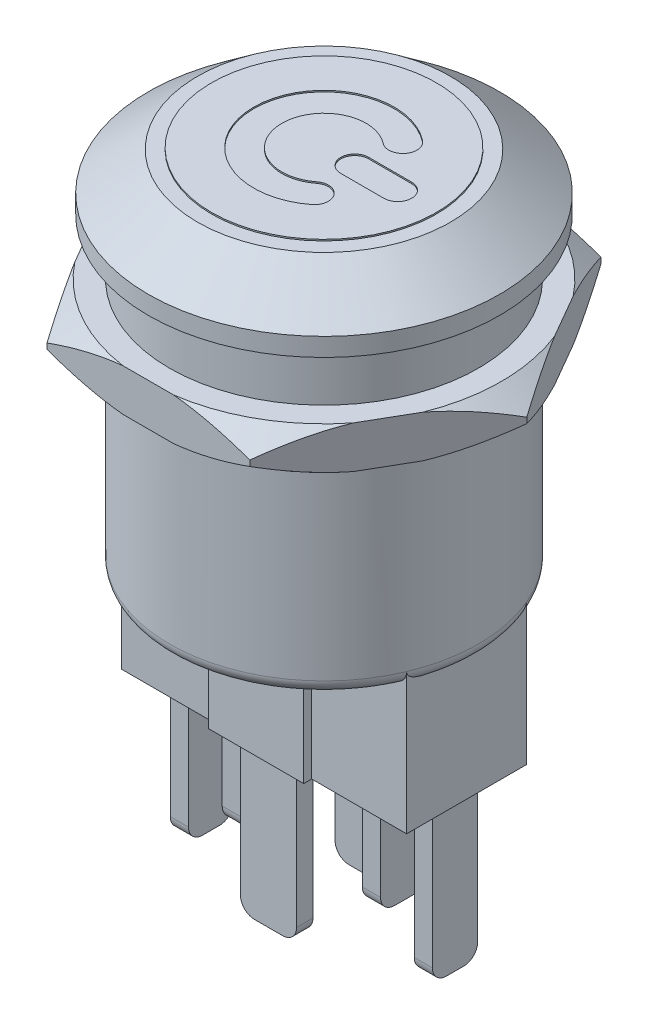
SolidWorks part; units mm, degrees
note: '?' marks a value the reader was unsure of.
ref_plane "前视基准面" through (0, 0, 0) normal (0, 0, 1) x (1, 0, 0)
ref_plane "上视基准面" through (0, 0, 0) normal (0, 1, 0) x (1, 0, 0)
ref_plane "右视基准面" through (0, 0, 0) normal (1, 0, 0) x (0, 0, -1)
sketch "草图1" plane through (0, 0, 0) normal (0, 1, 0) x (1, 0, 0)
  circle A0 centre (0, 0) radius 11
  dimension "D1" = 22
extrude "凸台-拉伸1" add sketch "草图1" along normal blind 15
sketch "草图8" plane through (0, 0, 0) normal (0, -1, 0) x (1, 0, 0)
  line L0 (-3.3825, 4.2596) -> (-3.3825, 4.8256)
  line L1 (10.1418, -4.2596) -> (3.3825, -4.2596)
  line L2 (10.1418, -4.2596) -> (10.1418, 4.2596)
  line L3 (10.1418, 4.2596) -> (3.3825, 4.2596)
  line L4 (-10.1418, -4.2596) -> (-10.1418, 4.2596)
  line L5 (10.1418, -4.2596) -> (-10.1418, 4.2596) construction
  line L6 (10.1418, 4.2596) -> (-10.1418, -4.2596) construction
  line L7 (-3.3825, -4.8256) -> (3.3825, -4.8256)
  line L8 (-3.3825, -4.8256) -> (-3.3825, -4.2596)
  line L9 (-3.3825, 4.8256) -> (3.3825, 4.8256)
  line L10 (3.3825, -4.8256) -> (3.3825, -4.2596)
  line L11 (-3.3825, -4.8256) -> (3.3825, 4.8256) construction
  line L12 (-3.3825, 4.8256) -> (3.3825, -4.8256) construction
  line L13 (-3.3825, -4.2596) -> (-10.1418, -4.2596)
  line L14 (-3.3825, 4.2596) -> (-10.1418, 4.2596)
  line L15 (3.3825, 4.2596) -> (3.3825, 4.8256)
  circle A0 centre (0, 0) radius 11 construction
  point P0 (0, 0)
  point P8 (0, 0)
extrude "凸台-拉伸5" add sketch "草图8" along normal blind 9
sketch "草图2" plane through (0, 0, 0) normal (0, -1, 0) x (1, 0, 0)
  line L0 (0, 0) -> (0, 7.9124) construction
  line L1 (3.6947, 0) -> (-4.9885, 0) construction
  line L2 (-5.6352, 1.6103) -> (-4.3417, 1.6103)
  line L3 (-4.3417, -1.6103) -> (-4.3417, 1.6103)
  line L4 (-5.6352, -1.6103) -> (-5.6352, 1.6103)
  line L5 (-5.6352, -1.6103) -> (-4.3417, -1.6103)
  line L6 (5.6352, -1.6103) -> (4.3417, -1.6103)
  line L7 (0, 0) -> (-8.6832, 0) construction
  line L8 (9.33, 1.6103) -> (8.0364, -1.6103) construction
  line L9 (9.33, -1.6103) -> (8.0364, 1.6103) construction
  line L10 (5.6352, 1.6103) -> (4.3417, 1.6103)
  line L11 (4.3417, -1.6103) -> (4.3417, 1.6103)
  line L12 (8.0364, -1.6103) -> (8.0364, 1.6103)
  line L13 (-9.33, -1.6103) -> (-8.0364, -1.6103)
  line L14 (-9.33, -1.6103) -> (-9.33, 1.6103)
  line L15 (-9.33, 1.6103) -> (-8.0364, 1.6103)
  line L16 (-8.0364, -1.6103) -> (-8.0364, 1.6103)
  line L17 (-9.33, -1.6103) -> (-8.0364, 1.6103) construction
  line L18 (-9.33, 1.6103) -> (-8.0364, -1.6103) construction
  line L19 (9.33, 1.6103) -> (8.0364, 1.6103)
  line L20 (9.33, -1.6103) -> (9.33, 1.6103)
  line L21 (9.33, -1.6103) -> (8.0364, -1.6103)
  line L22 (5.6352, -1.6103) -> (5.6352, 1.6103)
  line L23 (1.9974, -2.7841) -> (1.9974, -3.9524)
  line L24 (1.9974, 2.7841) -> (-1.9974, 2.7841)
  line L25 (1.9974, 2.7841) -> (1.9974, 3.9524)
  line L26 (1.9974, 3.9524) -> (-1.9974, 3.9524)
  line L27 (-1.9974, 2.7841) -> (-1.9974, 3.9524)
  line L28 (1.9974, 2.7841) -> (-1.9974, 3.9524) construction
  line L29 (1.9974, 3.9524) -> (-1.9974, 2.7841) construction
  line L30 (1.9974, -2.7841) -> (-1.9974, -2.7841)
  line L31 (1.9974, -3.9524) -> (-1.9974, -3.9524)
  line L32 (-1.9974, -2.7841) -> (-1.9974, -3.9524)
  point P0 (0, 3.3682)
  point P10 (-8.6832, 0)
  point P23 (8.6832, 0)
  dimension "D1" = 2
extrude "凸台-拉伸2" add sketch "草图2" along normal blind 11 from surface at 9 starting at face at (0, -9, 0)
sketch "草图9" plane through (0, 15, 0) normal (0, 1, 0) x (1, 0, 0)
  line L1 (-7.2169, 12.5) -> (-14.4338, 0)
  line L2 (-14.4338, 0) -> (-7.2169, -12.5)
  line L3 (-7.2169, -12.5) -> (7.2169, -12.5)
  line L4 (7.2169, -12.5) -> (14.4338, 0)
  line L5 (14.4338, 0) -> (7.2169, 12.5)
  line L6 (7.2169, 12.5) -> (-7.2169, 12.5)
  circle A0 centre (0, 0) radius 12.5 construction
  circle A1 centre (0, 0) radius 12.5 construction
  dimension "D1" = 25
extrude "凸台-拉伸6" add sketch "草图9" along normal blind 3
sketch "草图10" plane through (0, 18, 0) normal (0, 1, 0) x (1, 0, 0)
  circle A0 centre (0, 0) radius 12.5
  dimension "D1" = 25
extrude "凸台-拉伸7" add sketch "草图10" along normal blind 8
chamfer "倒角2" distance 2.7 distance2 3.5 1 edges at (0, 26, 12.5) first distance on face at (0, 26, 12.5)
sketch "草图12" plane through (0, 0, 0) normal (0, 0, 1) x (1, 0, 0)
  line L0 (-12.6295, 18) -> (-14.4338, 16.7)
  line L1 (-14.4338, 18) -> (-10.8253, 18) construction
  line L2 (-14.4338, 18) -> (-14.4338, 15) construction
  line L3 (-14.4338, 16.5) -> (-11.8121, 16.5) construction
  line L4 (-12.6295, 15) -> (-14.4338, 16.3)
  line L5 (-12.6295, 18) -> (-12.6295, 18.5)
  line L6 (-12.6295, 18.5) -> (-14.9338, 18.5)
  line L7 (-14.9338, 18.5) -> (-14.9338, 14.5)
  line L8 (-14.9338, 14.5) -> (-12.6295, 14.5)
  line L9 (-12.6295, 14.5) -> (-12.6295, 15)
  line L10 (-14.4338, 16.7) -> (-14.4338, 16.3)
  line L11 (0, 15) -> (0, 29.2248) construction
  line L12 (-11, 15) -> (11, 15) construction
  dimension "D1" = 1.3
  dimension "D2" = 0.5
  dimension "D3" = 0.5
  dimension "D4" = 0.5
revolve "切除-旋转1" cut sketch "草图12" angle 360 about L11
fillet "圆角2" radius 1 2 edges at (0, 0, -11) (0, 0, 11)
fillet "圆角3" radius 1 2 edges at (11, 0, 0) (-11, 0, 0)
sketch "草图13" plane through (0, 26, 0) normal (0, 1, 0) x (1, 0, 0)
  circle A0 centre (0, 0) radius 8
  dimension "D1" = 16
extrude "凸台-拉伸8" add sketch "草图13" along normal blind 0.1
sketch "草图14" plane through (0, 26.1, 0) normal (0, 1, 0) x (1, 0, 0)
  line L0 (5.2502, 0) -> (2.1899, 0) construction
  line L1 (5.2502, -0.9936) -> (2.1899, -0.9936)
  line L2 (5.2502, 0.9936) -> (2.1899, 0.9936)
  line L3 (2.3801, 1.8263) -> (3.9668, 3.0438)
  line L4 (2.3801, -1.8263) -> (3.9668, -3.0438)
  arc A0 (2.3801, 1.8263) -> (2.3801, -1.8263) centre (0, 0) ccw
  arc A1 (3.9668, 3.0438) -> (3.9668, -3.0438) centre (0, 0) ccw
  arc A2 (5.2502, -0.9936) -> (5.2502, 0.9936) centre (5.2502, 0) ccw
  arc A3 (2.1899, 0.9936) -> (2.1899, -0.9936) centre (2.1899, 0) ccw
  circle A4 centre (0, 0) radius 5 construction
  circle A5 centre (0, 0) radius 3 construction
  point P7 (3.72, 0)
  dimension "D1" = 6
  dimension "D3" = 75
  dimension "D2" = 2
extrude "切除-拉伸3" cut sketch "草图14" against normal blind 0.1
fillet "圆角4" radius 1 4 edges at (2.3801, 26.05, 1.8263) (3.9668, 26.05, 3.0438) (2.3801, 26.05, -1.8263) (3.9668, 26.05, -3.0438)
fillet "圆角5" radius 1 12 edges at (-8.6832, -20, -1.6103) (-8.6832, -20, 1.6103) (-4.9885, -20, -1.6103) (-4.9885, -20, 1.6103) (1.9974, -20, 3.3682) (-1.9974, -20, 3.3682) (-1.9974, -20, -3.3682) (1.9974, -20, -3.3682) (4.9885, -20, -1.6103) (4.9885, -20, 1.6103) (8.6832, -20, -1.6103) (8.6832, -20, 1.6103)
sketch "草图15" plane through (0, 18, 0) normal (0, 1, 0) x (1, 0, 0)
  circle A1 centre (0, 0) radius 12.5
  circle A2 centre (0, 0) radius 11
  circle A3 centre (0, 0) radius 11 construction
  circle A4 centre (0, 0) radius 12.5 construction
extrude "切除-拉伸4" cut sketch "草图15" along normal blind 4
sketch "草图16" plane through (0, 0, -3.9524) normal (0, 0, -1) x (-1, 0, 0)
  text T0 " LED"
extrude "切除-拉伸5" cut sketch "草图16" against normal blind 0.1
sketch "草图17" plane through (0, 0, -1.6103) normal (0, 0, -1) x (-1, 0, 0)
  line L0 (-4.3417, -19) -> (-4.3417, -9) construction
  line L1 (-5.6352, -20) -> (-4.3417, -20)
  line L2 (-5.6352, -20) -> (-5.6352, -17.5)
  line L3 (-5.6352, -17.5) -> (-4.3417, -17.5)
  line L4 (-4.3417, -20) -> (-4.3417, -17.5)
  line L5 (5.6352, -19) -> (5.6352, -9) construction
  line L6 (4.3417, -20) -> (5.6352, -20)
  line L7 (4.3417, -20) -> (4.3417, -17.5)
  line L8 (4.3417, -17.5) -> (5.6352, -17.5)
  line L9 (5.6352, -20) -> (5.6352, -17.5)
  dimension "D1" = 2.5
extrude "切除-拉伸6" cut sketch "草图17" against normal through all
fillet "圆角6" radius 1 4 edges at (-4.9885, -17.5, 1.6103) (-4.9885, -17.5, -1.6103) (4.9885, -17.5, -1.6103) (4.9885, -17.5, 1.6103)
sketch "草图18" plane through (0, -20, 0) normal (0, -1, 0) x (1, 0, 0)
  point P0 (8.761, 0)
  point P1 (0, -3.4135)
  point P2 (0, 3.281)
  point P3 (-8.7366, 0)
other "连接点1" parameters "直径"=2.2, "端头长度"=1
ref_axis "基准轴1" through (8.761, -30, 0) along (0, 1, 0)?
other "连接点2" parameters "直径"=2, "端头长度"=1
ref_axis "基准轴2" through (-8.7366, -30, 0) along (0, 1, 0)?
other "连接点3" parameters "直径"=2, "端头长度"=1
ref_axis "基准轴3" through (0, -30, -3.4135) along (0, 1, 0)?
other "连接点4" parameters "直径"=2, "端头长度"=1
ref_axis "基准轴4" through (0, -30, 3.281) along (0, 1, 0)?
